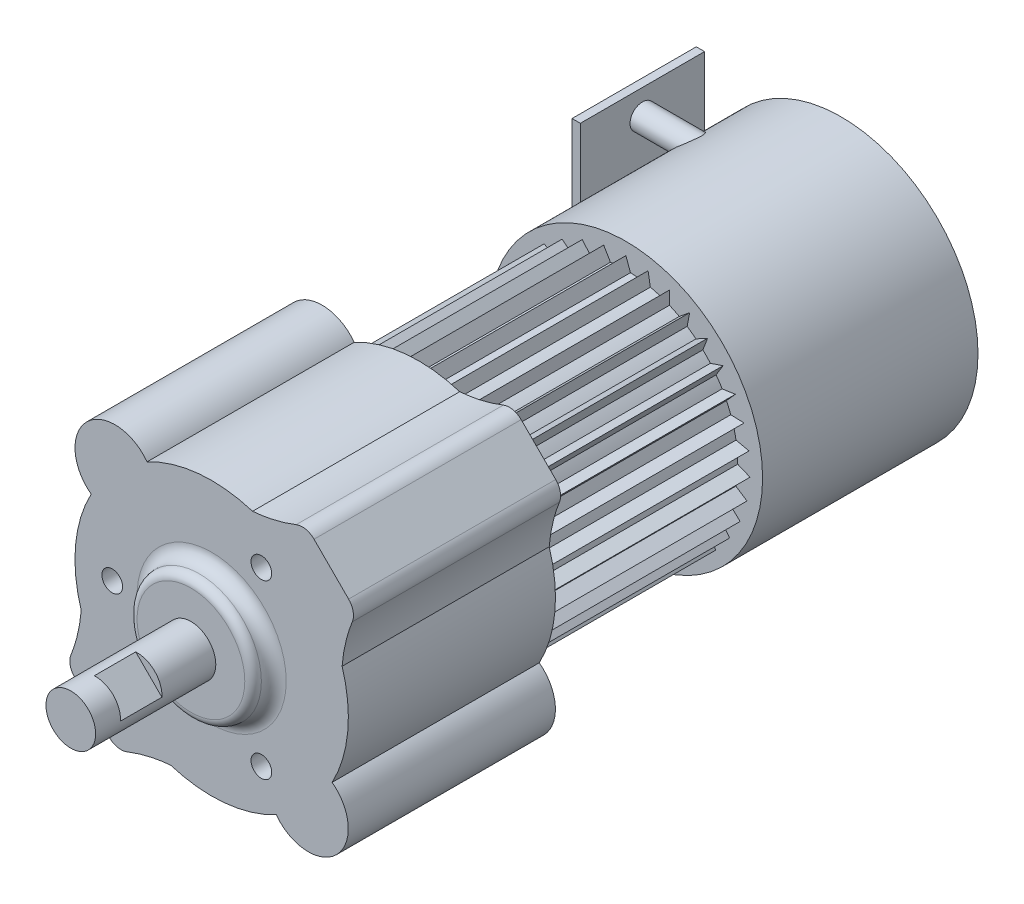
SolidWorks part; units mm, degrees
ref_plane "Front Plane" through (0, 0, 0) normal (0, 0, 1) x (1, 0, 0)
ref_plane "Top Plane" through (0, 0, 0) normal (0, 1, 0) x (1, 0, 0)
ref_plane "Right Plane" through (0, 0, 0) normal (1, 0, 0) x (0, 0, -1)
sketch "Sketch1" plane through (0, 0, 0) normal (0, 0, 1) x (1, 0, 0)
  line L0 (11.392, 17.5) -> (17.5, 11.392)
  line L7 (-17.5, -11.392) -> (-11.392, -17.5)
  arc A0 (-14.5435, 7.7934) -> (-15.7433, -4.9394) centre (0, 0) ccw
  arc A1 (-7.7934, 14.5435) -> (-14.5435, 7.7934) centre (-11.6673, 11.6673) ccw
  arc A2 (14.5435, -7.7934) -> (7.7934, -14.5435) centre (11.6673, -11.6673) cw
  arc A3 (4.9394, 15.7433) -> (-7.7934, 14.5435) centre (0, 0) ccw
  arc A4 (14.5435, -7.7934) -> (15.7433, 4.9394) centre (0, 0) ccw
  arc A5 (-4.9394, -15.7433) -> (7.7934, -14.5435) centre (0, 0) ccw
  spline S0 degree 2 poles (11.392, 17.5) (8.3367, 16.021) (4.9394, 15.7433) knots 0 0 0 1 1 1
  spline S1 degree 2 poles (-17.5, -11.392) (-16.021, -8.3367) (-15.7433, -4.9394) knots 0 0 0 1 1 1
  spline S2 degree 2 poles (-11.392, -17.5) (-8.3367, -16.021) (-4.9394, -15.7433) knots 0 0 0 1 1 1
  spline S3 degree 2 poles (17.5, 11.392) (16.021, 8.3367) (15.7433, 4.9394) knots 0 0 0 1 1 1
  point P0 (0, 0)
extrude "Boss-Extrude1" add sketch "Sketch1" along normal blind 25
fillet "Fillet1" radius 2 4 edges at (-11.392, -17.5, 12.5) (-17.5, -11.392, 12.5) (17.5, 11.392, 12.5) (11.392, 17.5, 12.5)
sketch "Sketch3" plane through (0, 0, 0) normal (0, 0, -1) x (-1, 0, 0)
  line L3 (-0.552, 13.4887) -> (0, 15)
  line L4 (0, 15) -> (0.552, 13.4887)
  line L5 (2.6784, 14.7589) -> (2.9516, 13.1734)
  line L6 (1.8654, 13.3705) -> (2.6784, 14.7589)
  line L7 (5.2706, 14.0435) -> (5.2564, 12.4347)
  line L8 (4.2228, 12.8225) -> (5.2706, 14.0435)
  line L9 (7.6935, 12.8767) -> (7.3922, 11.2963)
  line L10 (6.4445, 11.8625) -> (7.6935, 12.8767)
  line L11 (9.8691, 11.2961) -> (9.2904, 9.7948)
  line L12 (8.4591, 10.5211) -> (9.8691, 11.2961)
  line L13 (11.7275, 9.3523) -> (10.89, 7.9785)
  line L14 (10.2018, 8.8416) -> (11.7275, 9.3523)
  line L15 (13.2089, 7.108) -> (12.1397, 5.9058)
  line L16 (11.6165, 6.8779) -> (13.2089, 7.108)
  line L17 (14.2658, 4.6353) -> (12.9991, 3.6433)
  line L18 (12.658, 4.6932) -> (14.2658, 4.6353)
  line L19 (14.8642, 2.0135) -> (13.4407, 1.2637)
  line L20 (13.2925, 2.3576) -> (14.8642, 2.0135)
  line L21 (14.9849, -0.673) -> (13.4504, -1.1566)
  line L22 (13.4999, -0.0538) -> (14.9849, -0.673)
  line L23 (14.6239, -3.3378) -> (13.0277, -3.5396)
  line L24 (13.2733, -2.4634) -> (14.6239, -3.3378)
  line L25 (13.7929, -5.8954) -> (12.1863, -5.809)
  line L26 (12.6202, -4.7939) -> (13.7929, -5.8954)
  line L27 (12.5186, -8.2635) -> (10.9532, -7.8915)
  line L28 (11.5614, -6.9702) -> (12.5186, -8.2635)
  line L29 (10.8419, -10.3659) -> (9.3681, -9.7205)
  line L30 (10.131, -8.9226) -> (10.8419, -10.3659)
  line L31 (8.8168, -12.1353) -> (7.4819, -11.237)
  line L32 (8.375, -10.5882) -> (8.8168, -12.1353)
  line L33 (6.5083, -13.5145) -> (5.3552, -12.3924)
  line L34 (6.3498, -11.9134) -> (6.5083, -13.5145)
  line L35 (3.9906, -14.4594) -> (3.0564, -13.1495)
  line L36 (4.1206, -12.8558) -> (3.9906, -14.4594)
  line L37 (1.3446, -14.9396) -> (0.6594, -13.4839)
  line L38 (1.7589, -13.3849) -> (1.3446, -14.9396)
  line L39 (-1.3446, -14.9396) -> (-1.7589, -13.3849)
  line L40 (-0.6594, -13.4839) -> (-1.3446, -14.9396)
  line L41 (-3.9906, -14.4594) -> (-4.1206, -12.8558)
  line L42 (-3.0564, -13.1495) -> (-3.9906, -14.4594)
  line L43 (-6.5083, -13.5145) -> (-6.3498, -11.9134)
  line L44 (-5.3552, -12.3924) -> (-6.5083, -13.5145)
  line L45 (-8.8168, -12.1353) -> (-8.375, -10.5882)
  line L46 (-7.4819, -11.237) -> (-8.8168, -12.1353)
  line L47 (-10.8419, -10.3659) -> (-10.131, -8.9226)
  line L48 (-9.3681, -9.7205) -> (-10.8419, -10.3659)
  line L49 (-12.5186, -8.2635) -> (-11.5614, -6.9702)
  line L50 (-10.9532, -7.8915) -> (-12.5186, -8.2635)
  line L51 (-13.7929, -5.8954) -> (-12.6202, -4.7939)
  line L52 (-12.1863, -5.809) -> (-13.7929, -5.8954)
  line L53 (-14.6239, -3.3378) -> (-13.2733, -2.4634)
  line L54 (-13.0277, -3.5396) -> (-14.6239, -3.3378)
  line L55 (-14.9849, -0.673) -> (-13.4999, -0.0538)
  line L56 (-13.4504, -1.1566) -> (-14.9849, -0.673)
  line L57 (-14.8642, 2.0135) -> (-13.2925, 2.3576)
  line L58 (-13.4407, 1.2637) -> (-14.8642, 2.0135)
  line L59 (-14.2658, 4.6353) -> (-12.658, 4.6932)
  line L60 (-12.9991, 3.6433) -> (-14.2658, 4.6353)
  line L61 (-13.2089, 7.108) -> (-11.6165, 6.8779)
  line L62 (-12.1397, 5.9058) -> (-13.2089, 7.108)
  line L63 (-11.7275, 9.3523) -> (-10.2018, 8.8416)
  line L64 (-10.89, 7.9785) -> (-11.7275, 9.3523)
  line L65 (-9.8691, 11.2961) -> (-8.4591, 10.5211)
  line L66 (-9.2904, 9.7948) -> (-9.8691, 11.2961)
  line L67 (-7.6935, 12.8767) -> (-6.4445, 11.8625)
  line L68 (-7.3922, 11.2963) -> (-7.6935, 12.8767)
  line L69 (-5.2706, 14.0435) -> (-4.2228, 12.8225)
  line L70 (-5.2564, 12.4347) -> (-5.2706, 14.0435)
  line L71 (-2.6784, 14.7589) -> (-1.8654, 13.3705)
  line L72 (-2.9516, 13.1734) -> (-2.6784, 14.7589)
  arc A1 (1.8654, 13.3705) -> (0.552, 13.4887) centre (0, 0) ccw
  arc A2 (4.2228, 12.8225) -> (2.9516, 13.1734) centre (0, 0) ccw
  arc A3 (6.4445, 11.8625) -> (5.2564, 12.4347) centre (0, 0) ccw
  arc A4 (8.4591, 10.5211) -> (7.3922, 11.2963) centre (0, 0) ccw
  arc A5 (10.2018, 8.8416) -> (9.2904, 9.7948) centre (0, 0) ccw
  arc A6 (11.6165, 6.8779) -> (10.89, 7.9785) centre (0, 0) ccw
  arc A7 (12.658, 4.6932) -> (12.1397, 5.9058) centre (0, 0) ccw
  arc A8 (13.2925, 2.3576) -> (12.9991, 3.6433) centre (0, 0) ccw
  arc A9 (13.4999, -0.0538) -> (13.4407, 1.2637) centre (0, 0) ccw
  arc A10 (13.2733, -2.4634) -> (13.4504, -1.1566) centre (0, 0) ccw
  arc A11 (12.6202, -4.7939) -> (13.0277, -3.5396) centre (0, 0) ccw
  arc A12 (11.5614, -6.9702) -> (12.1863, -5.809) centre (0, 0) ccw
  arc A13 (10.131, -8.9226) -> (10.9532, -7.8915) centre (0, 0) ccw
  arc A14 (8.375, -10.5882) -> (9.3681, -9.7205) centre (0, 0) ccw
  arc A15 (6.3498, -11.9134) -> (7.4819, -11.237) centre (0, 0) ccw
  arc A16 (4.1206, -12.8558) -> (5.3552, -12.3924) centre (0, 0) ccw
  arc A17 (1.7589, -13.3849) -> (3.0564, -13.1495) centre (0, 0) ccw
  arc A18 (-0.6594, -13.4839) -> (0.6594, -13.4839) centre (0, 0) ccw
  arc A19 (-3.0564, -13.1495) -> (-1.7589, -13.3849) centre (0, 0) ccw
  arc A20 (-5.3552, -12.3924) -> (-4.1206, -12.8558) centre (0, 0) ccw
  arc A21 (-0.552, 13.4887) -> (-1.8654, 13.3705) centre (0, 0) ccw
  arc A22 (-2.9516, 13.1734) -> (-4.2228, 12.8225) centre (0, 0) ccw
  arc A23 (-5.2564, 12.4347) -> (-6.4445, 11.8625) centre (0, 0) ccw
  arc A24 (-7.3922, 11.2963) -> (-8.4591, 10.5211) centre (0, 0) ccw
  arc A25 (-9.2904, 9.7948) -> (-10.2018, 8.8416) centre (0, 0) ccw
  arc A26 (-10.89, 7.9785) -> (-11.6165, 6.8779) centre (0, 0) ccw
  arc A27 (-12.1397, 5.9058) -> (-12.658, 4.6932) centre (0, 0) ccw
  arc A28 (-12.9991, 3.6433) -> (-13.2925, 2.3576) centre (0, 0) ccw
  arc A29 (-13.4407, 1.2637) -> (-13.4999, -0.0538) centre (0, 0) ccw
  arc A30 (-13.4504, -1.1566) -> (-13.2733, -2.4634) centre (0, 0) ccw
  arc A31 (-13.0277, -3.5396) -> (-12.6202, -4.7939) centre (0, 0) ccw
  arc A32 (-12.1863, -5.809) -> (-11.5614, -6.9702) centre (0, 0) ccw
  arc A33 (-10.9532, -7.8915) -> (-10.131, -8.9226) centre (0, 0) ccw
  arc A34 (-9.3681, -9.7205) -> (-8.375, -10.5882) centre (0, 0) ccw
  arc A35 (-7.4819, -11.237) -> (-6.3498, -11.9134) centre (0, 0) ccw
  point P111 (0, 0)
  dimension "D1" = 35
extrude "Boss-Extrude2" add sketch "Sketch3" along normal blind 25
sketch "Sketch4" plane through (0, 0, -25) normal (0, 0, -1) x (-1, 0, 0)
  circle A0 centre (0, 0) radius 16.5
extrude "Boss-Extrude5" add sketch "Sketch4" along normal blind 26 contours A0
sketch "Sketch6" plane through (0, 0, -51) normal (0, 0, -1) x (-1, 0, 0)
  line L1 (16.5, -15.079) -> (16.5, 15.079)
  line L2 (16.5, 15.079) -> (17.5, 15.079)
  line L3 (17.5, 15.079) -> (17.5, -15.079)
  line L4 (16.5, -15.079) -> (17.5, -15.079)
  point P11 (17.5, 0)
extrude "Boss-Extrude6" add sketch "Sketch6" against normal blind 15 separate body
sketch "Sketch7" plane through (-17.5, 0, 0) normal (-1, 0, 0) x (0, 0, 1)
  circle A0 centre (-43.5, 12.0662) radius 1.5
  circle A1 centre (-43.5, -12.0662) radius 1.5
extrude "Boss-Extrude9" add sketch "Sketch7" against normal blind 15
sketch "Sketch8" plane through (0, 0, 25) normal (0, 0, 1) x (1, 0, 0)
  circle A0 centre (0, 0) radius 3
  dimension "D1" = 6
extrude "Boss-Extrude10" add sketch "Sketch8" along normal blind 17
sketch "Sketch9" plane through (0, 0, 25) normal (0, 0, 1) x (1, 0, 0)
  circle A0 centre (0, 0) radius 7.5
extrude "Boss-Extrude11" add sketch "Sketch9" along normal blind 2.5
fillet "Fillet2" radius 1.5 1 edges at (7.5, 0, 25)
fillet "Fillet3" radius 1 1 edges at (7.5, 0, 27.5)
ref_plane "Plane1" through (2.1213, 2.1213, 0) normal (0.7071, 0.7071, 0) x (0.7071, -0.7071, 0)
sketch "Sketch10" plane through (2.1213, 2.1213, 0) normal (0.7071, 0.7071, 0) x (0.7071, -0.7071, 0)
  line L0 (-3, -42) -> (-3, -39) construction
  line L1 (-3, -27.5) -> (-3, -42) construction
  line L3 (-3, -39) -> (3, -39)
  line L4 (-3, -39) -> (-3, -34)
  line L5 (-3, -34) -> (3, -34)
  line L6 (3, -39) -> (3, -34)
  dimension "D1" = 3
  dimension "D2" = 5
  dimension "D3" = 6
extrude "Cut-Extrude1" cut sketch "Sketch10" against normal blind 1
sketch "Sketch12" plane through (0, 0, 25) normal (0, 0, 1) x (1, 0, 0)
  line L0 (0, 0) -> (-12, 0) construction
  circle A0 centre (-12, 0) radius 1.25
  circle A1 centre (6, 10.3923) radius 1.25
  circle A2 centre (6, -10.3923) radius 1.25
  point P11 (0, 0)
  dimension "D2" = 2.5
  dimension "D4" = 2.5
  dimension "D1" = 12
  dimension "D3" = 3
extrude "Cut-Extrude2" cut sketch "Sketch12" against normal blind 4
